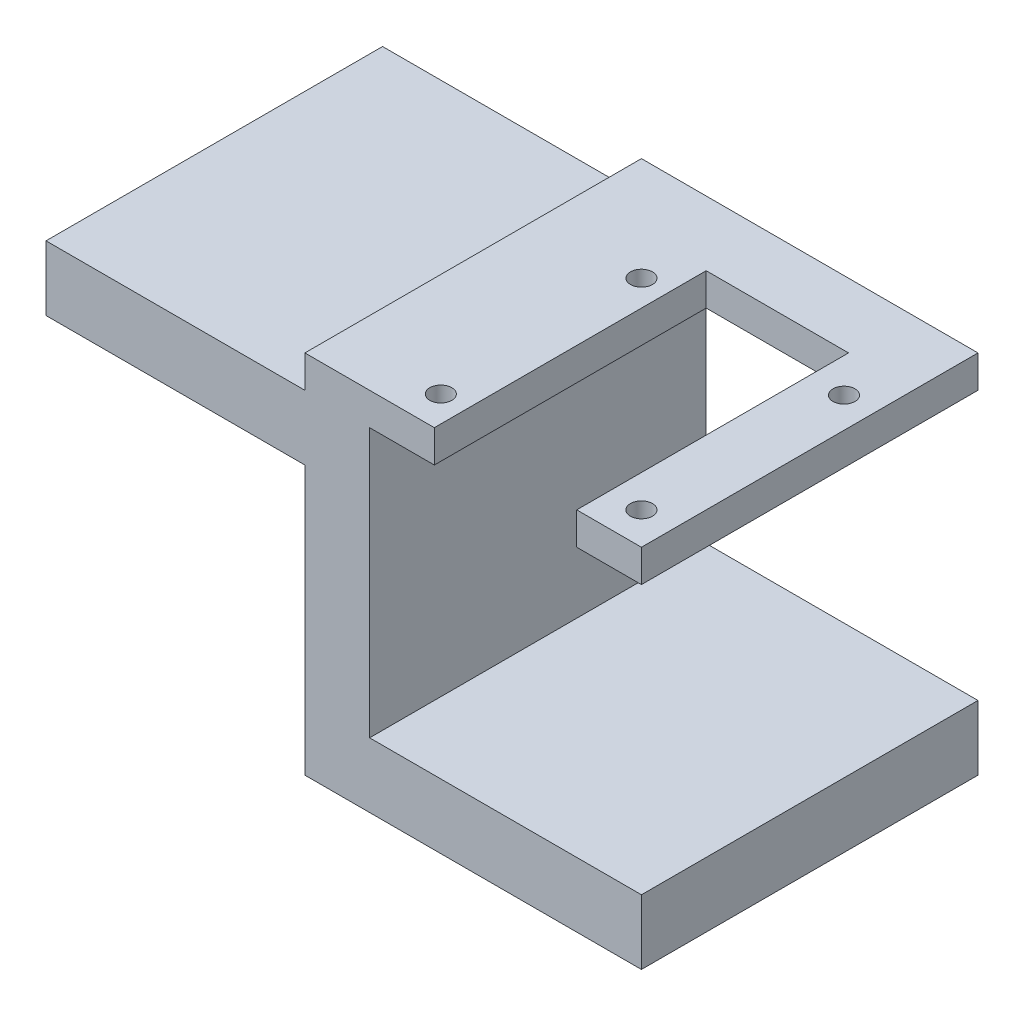
SolidWorks part; units mm, degrees
ref_plane "Front Plane" through (0, 0, 0) normal (0, 0, 1) x (1, 0, 0)
ref_plane "Top Plane" through (0, 0, 0) normal (0, 1, 0) x (1, 0, 0)
ref_plane "Right Plane" through (0, 0, 0) normal (1, 0, 0) x (0, 0, -1)
sketch "Sketch7" plane through (0, 0, 0) normal (0, 0, 1) x (1, 0, 0)
  line L0 (-65, -22.5) -> (-25, -22.5) construction
  line L1 (65, -35) -> (-65, -35)
  line L2 (65, -35) -> (65, 35)
  line L3 (65, 35) -> (-65, 35)
  line L4 (-65, -35) -> (-65, 35)
  line L5 (65, -35) -> (-65, 35) construction
  line L6 (65, 35) -> (-65, -35) construction
  line L7 (-65, -35) -> (-23.5286, -35)
  line L8 (-65, -35) -> (-65, -17.3169)
  line L11 (-25, -10) -> (-65, -10)
  line L12 (-25, -10) -> (-25, -35)
  line L13 (-25, -35) -> (-65, -35)
  line L14 (-65, -10) -> (-65, -35)
  line L15 (-25, -10) -> (-65, -35) construction
  line L16 (-25, -35) -> (-65, -10) construction
  line L17 (-45, -10) -> (-45, -35) construction
  line L19 (-25, 0) -> (-65, 0)
  line L20 (-25, 0) -> (-25, -10)
  line L21 (-25, -10) -> (-65, -10)
  line L22 (-65, 0) -> (-65, -10)
  line L23 (-25, 0) -> (-65, -10) construction
  line L24 (-25, -10) -> (-65, 0) construction
  line L25 (-15, -51.5018) -> (-25, -51.5018)
  line L26 (-15, -51.5018) -> (-15, 0)
  line L27 (-15, 0) -> (-25, 0)
  line L28 (-25, -51.5018) -> (-25, 0)
  line L29 (-15, -51.5018) -> (-25, 0) construction
  line L30 (-15, 0) -> (-25, -51.5018) construction
  line L31 (27, -41.5018) -> (-15, -41.5018)
  line L32 (27, -41.5018) -> (27, -51.5018)
  line L33 (27, -51.5018) -> (-15, -51.5018)
  line L34 (-15, -41.5018) -> (-15, -51.5018)
  line L35 (27, -41.5018) -> (-15, -51.5018) construction
  line L36 (27, -51.5018) -> (-15, -41.5018) construction
  line L37 (27, 5) -> (-15, 5)
  line L38 (27, 5) -> (27, 0)
  line L39 (27, 0) -> (-15, 0)
  line L40 (-15, 5) -> (-15, 0)
  line L41 (27, 5) -> (-15, 0) construction
  line L42 (27, 0) -> (-15, 5) construction
  line L43 (-5, 0) -> (-15, 0)
  line L44 (-5, 0) -> (-5, 5)
  line L45 (-5, 5) -> (-15, 5)
  line L46 (-15, 0) -> (-15, 5)
  line L47 (-5, 0) -> (-15, 5) construction
  line L48 (-5, 5) -> (-15, 0) construction
  line L49 (17, 0) -> (27, 0)
  line L50 (17, 0) -> (17, 5)
  line L51 (17, 5) -> (27, 5)
  line L52 (27, 0) -> (27, 5)
  line L53 (17, 0) -> (27, 5) construction
  line L54 (17, 5) -> (27, 0) construction
  line L55 (-25, 5) -> (-15, 5)
  line L56 (-25, 5) -> (-25, 0)
  line L57 (-25, 0) -> (-15, 0)
  line L58 (-15, 5) -> (-15, 0)
  line L59 (-25, 5) -> (-15, 0) construction
  line L60 (-25, 0) -> (-15, 5) construction
  circle A0 centre (-55, -22.5) radius 2.7
  circle A1 centre (-35, -22.5) radius 2.7
  point P0 (0, 0)
  point P6 (-45, -22.5)
  point P20 (-45, -5)
  point P21 (-20, -25.7509)
  point P24 (6, -46.5018)
  point P28 (6, 2.5)
  point P32 (-10, 2.5)
  point P36 (22, 2.5)
  point P39 (-20, 2.5)
  dimension "D5" = 5.4
  dimension "D1" = 130
  dimension "D2" = 70
  dimension "D3" = 25
  dimension "D4" = 40
  dimension "D6" = 10
  dimension "D7" = 10
  dimension "D8" = 10
  dimension "D9" = 10
  dimension "D10" = 10
  dimension "D11" = 5
  dimension "D12" = 42
  dimension "D13" = 10
  dimension "D14" = 10
extrude "Boss-Extrude5" add sketch "Sketch7" along normal blind 10 contours L12 L11 L4 L7 A1 A0 | L39 L50 L37 L44 region at (-45, -22.5, 0) region at (6, 2.5, 0)
extrude "Boss-Extrude6" add sketch "Sketch7<4>" along normal blind 52 contours L33 L32 L31 L26 | L28 L25 L26 L1 | L26 L27 L20 L12 L1 | L55 L56 L27 L40 | L39 L44 L37 L40 | L50 L39 L38 L37 | L20 L19 L4 L11 region at (-20, -43.2509, 0) region at (-20, -17.5, 0) region at (-45, -5, 0) region at (6, -46.5018, 0) region at (-10, 2.5, 0) region at (-20, 2.5, 0) region at (22, 2.5, 0)
sketch "Sketch7<4>" plane through (0, 0, 0) normal (0, 0, 1) x (1, 0, 0) same geometry as "Sketch7"
sketch "Sketch8" plane through (0, 5, 0) normal (0, 1, 0) x (1, 0, 0)
  line L0 (27, -52) -> (27, 0) construction
  line L1 (27, -52) -> (17, -52) construction
  circle A0 centre (22, -47) radius 1.7
  circle A1 centre (22.2969, -16) radius 1.7
  circle A2 centre (-9, -47) radius 1.7
  circle A3 centre (-9, -16) radius 1.7
  point P12 (0, 0)
  point P13 (0, 0)
  point P14 (0, 0)
  point P15 (0, 0)
  point P16 (0, 0)
  dimension "D1" = 3.4
  dimension "D2" = 5
  dimension "D3" = 5
  dimension "D4" = 31
  dimension "D5" = 31
extrude "Cut-Extrude3" cut sketch "Sketch8" against normal up to next
